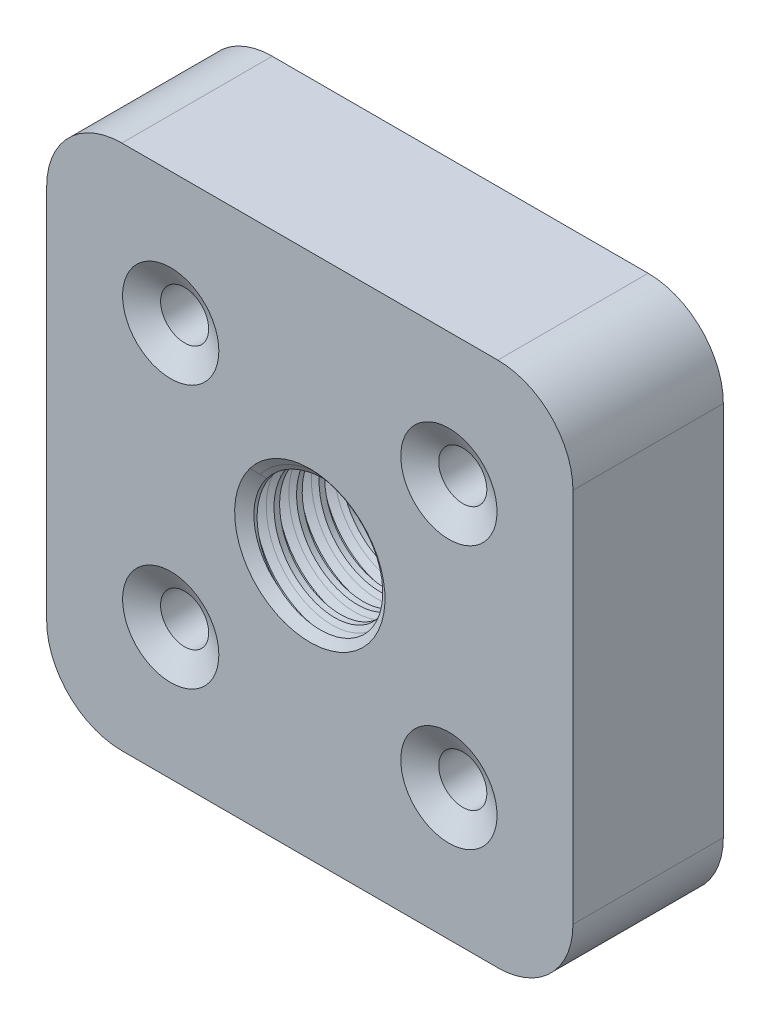
SolidWorks part; units mm, degrees
ref_plane "Front Plane" through (0, 0, 0) normal (0, 0, 1) x (1, 0, 0)
ref_plane "Top Plane" through (0, 0, 0) normal (0, 1, 0) x (1, 0, 0)
ref_plane "Right Plane" through (0, 0, 0) normal (1, 0, 0) x (0, 0, -1)
sketch "Sketch1" plane through (0, 0, 0) normal (0, 0, 1) x (1, 0, 0)
  line L1 (-17.5, -17.5) -> (17.5, -17.5)
  line L2 (-17.5, -17.5) -> (-17.5, 17.5)
  line L3 (-17.5, 17.5) -> (17.5, 17.5)
  line L4 (17.5, -17.5) -> (17.5, 17.5)
  line L5 (-17.5, -17.5) -> (17.5, 17.5) construction
  line L6 (-17.5, 17.5) -> (17.5, -17.5) construction
  line L7 (-9.25, -8.75) -> (9.25, -8.75)
  line L8 (-9.25, -8.75) -> (-9.25, 8.75)
  line L9 (-9.25, 8.75) -> (9.25, 8.75)
  line L10 (9.25, -8.75) -> (9.25, 8.75)
  line L11 (-9.25, -8.75) -> (9.25, 8.75) construction
  line L12 (-9.25, 8.75) -> (9.25, -8.75) construction
  circle A0 centre (0, 0) radius 4.188
  circle A1 centre (-9.25, 8.75) radius 1.6
  circle A2 centre (9.25, 8.75) radius 1.6
  circle A3 centre (-9.25, -8.75) radius 1.6
  circle A4 centre (9.25, -8.75) radius 1.6
  point P0 (0, 0)
  dimension "D3" = 8.376
  dimension "D6" = 3.2
  dimension "D7" = 3.2
  dimension "D8" = 3.2
  dimension "D9" = 3.2
  dimension "D1" = 35
  dimension "D2" = 35
  dimension "D4" = 18.5
  dimension "D5" = 17.5
extrude "Boss-Extrude1" add sketch "Sketch1" along normal blind 10 contours L1 L4 L3 L2 A4 L7 A3 L8 A1 L9 A2 L10 | A4 L10 A2 L9 A1 L8 A3 L7 A0 region at (-17.005, 0, 0) region at (-7.9386, -7.4386, 0)
ref_plane "Plane1" through (0, 0, 12.5) normal (0, 0, 1) x (1, 0, 0)
sketch "Sketch2" plane through (0, 0, 12.5) normal (0, 0, 1) x (1, 0, 0)
  circle A0 centre (0, 0) radius 4.513
  dimension "D1" = 9.026
curve "Helix/Spiral1" pitch 1.5 height 15 radius 4.513 centre (0, 0, 12.5) axis (0, 0, -1) start towards (1, 0, 0)
sketch "Sketch3" plane through (0, 0, 0) normal (0, 1, 0) x (1, 0, 0)
  line L0 (0, 0) -> (0, -12.5) construction
  line L1 (0, -12.5) -> (4.513, -12.5) construction
  line L2 (0, -12.5) -> (4.188, -12.5) construction
  line L3 (0, -12.5) -> (5, -12.5) construction
  line L4 (5, -12.4062) -> (5, -12.5938) construction
  line L5 (4.513, -12.875) -> (4.513, -12.125) construction
  line L6 (5, -12.5938) -> (4.513, -12.875)
  line L7 (4.513, -12.875) -> (4.188, -13.0627)
  line L8 (5, -12.4062) -> (4.513, -12.125)
  line L9 (4.513, -12.125) -> (4.188, -11.9373)
  line L10 (4.188, -12.5) -> (4.188, -13.0627)
  line L11 (4.188, -12.5) -> (4.188, -11.9373)
  line L12 (5, -12.5938) -> (5, -12.4062)
  dimension "D1" = 12.5
  dimension "D2" = 4.513
  dimension "D3" = 4.188
  dimension "D4" = 5
  dimension "D5" = 0.0938
  dimension "D6" = 0.1875
  dimension "D7" = 0.375
  dimension "D8" = 0.75
sweep "Cut-Sweep1" cut profiles "Sketch3" path "Helix/Spiral1" align with end faces yes
sketch "Sketch4" plane through (0, 0, 0) normal (0, 1, 0) x (1, 0, 0)
  line L0 (0, 0) -> (0, -10) construction
  line L1 (-17.5, -10) -> (17.5, -10) construction
  line L2 (0, -10) -> (5, -10) construction
  line L3 (5, 0) -> (0, 0) construction
  line L4 (-17.5, 0) -> (17.5, 0) construction
  line L5 (5, -10) -> (4, -10)
  line L6 (4, -10) -> (4, -9.4226)
  line L7 (4, -9.4226) -> (5, -10)
  line L8 (5, 0) -> (4, 0)
  line L9 (4, 0) -> (4, -0.5774)
  line L10 (4, -0.5774) -> (5, 0)
  dimension "D1" = 5
  dimension "D2" = 5
  dimension "D3" = 1
  dimension "D4" = 30
  dimension "D5" = 1
  dimension "D6" = 30
revolve "Cut-Revolve1" cut sketch "Sketch4" angle 360 about L0
fillet "Fillet1" radius 5 4 edges at (17.5, -17.5, 5) (-17.5, -17.5, 5) (-17.5, 17.5, 5) (17.5, 17.5, 5)
sketch "Sketch5" plane through (0, 0, 10) normal (0, 0, 1) x (1, 0, 0)
  circle A0 centre (-9.25, 8.75) radius 3.2
  circle A1 centre (9.25, 8.75) radius 3.2
  circle A2 centre (-9.25, -8.75) radius 3.2
  circle A3 centre (9.25, -8.75) radius 3.2
  dimension "D1" = 6.4
  dimension "D2" = 6.4
  dimension "D3" = 6.4
  dimension "D4" = 6.4
extrude "Cut-Extrude1" cut sketch "Sketch5" against normal blind 1 draft 60
